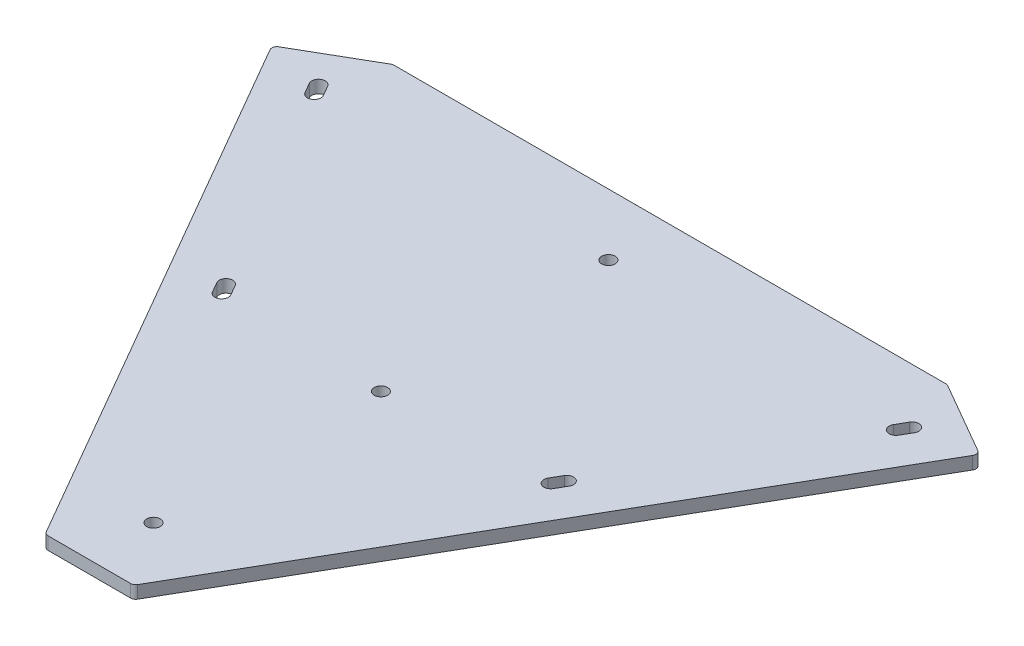
SolidWorks part; units mm, degrees
material "PC High Viscosity"
ref_plane "Front Plane" through (0, 0, 0) normal (0, 0, 1) x (1, 0, 0)
ref_plane "Top Plane" through (0, 0, 0) normal (0, 1, 0) x (1, 0, 0)
ref_plane "Right Plane" through (0, 0, 0) normal (1, 0, 0) x (0, 0, -1)
sketch "Sketch1" plane through (0, 0, 0) normal (0, 1, 0) x (1, 0, 0)
  line L0 (-95.25, 164.9778) -> (-56.7552, 187.2028) construction
  line L5 (-22.225, -99.5201) -> (22.225, -99.5201) construction
  line L6 (-22.225, -99.5201) -> (-22.225, 357.6799) construction
  line L7 (-22.225, 357.6799) -> (22.225, 357.6799) construction
  line L8 (22.225, -99.5201) -> (22.225, 357.6799) construction
  line L9 (-95.25, 164.9778) -> (-577.85, 1000.8656) construction
  line L10 (-56.7552, 187.2028) -> (-539.3552, 1023.0906) construction
  line L11 (-577.85, 1000.8656) -> (-539.3552, 1023.0906) construction
  line L16 (0, 0) -> (0, 1023.0906) construction
  line L17 (577.85, 1000.8656) -> (539.3552, 1023.0906) construction
  line L18 (56.7552, 187.2028) -> (539.3552, 1023.0906) construction
  line L19 (95.25, 164.9778) -> (577.85, 1000.8656) construction
  line L20 (95.25, 164.9778) -> (56.7552, 187.2028) construction
  line L21 (-155.1802, 357.6799) -> (-193.675, 335.4549) construction
  line L22 (-155.1802, 357.6799) -> (-177.4052, 396.1748) construction
  line L23 (-193.675, 335.4549) -> (-215.9, 373.9498) construction
  line L24 (-177.4052, 396.1748) -> (-215.9, 373.9498) construction
  line L25 (193.675, 335.4549) -> (215.9, 373.9498) construction
  line L26 (177.4052, 396.1748) -> (215.9, 373.9498) construction
  line L27 (155.1802, 357.6799) -> (177.4052, 396.1748) construction
  line L28 (155.1802, 357.6799) -> (193.675, 335.4549) construction
  line L29 (-177.8, 307.9586) -> (-22.225, 38.4948)
  line L30 (-22.225, 38.4948) -> (22.225, 38.4948)
  line L31 (-177.8, 307.9586) -> (-139.3052, 330.1836)
  line L32 (-139.3052, 330.1836) -> (139.3052, 330.1836)
  line L33 (177.8, 307.9586) -> (22.225, 38.4948)
  line L34 (177.8, 307.9586) -> (139.3052, 330.1836)
  point P18 (0, 357.6799)
  point P30 (0, 38.4948)
  point P32 (0, 330.1836)
  dimension "D1" = 60
  dimension "D2" = 965.2
  dimension "D3" = 190.5
  dimension "D4" = 44.45
  dimension "D5" = 196.85
  dimension "D6" = 34.5302
  dimension "D7" = 31.75
  dimension "D8" = 457.2
  dimension "D9" = 291.6888
  dimension "D10" = 311.15
extrude "Boss-Extrude1" add sketch "Sketch1" along normal blind 6.35
hole_wizard "1/4 Clearance Hole1" positions "Sketch2" profile "Sketch3" hole size "1/4" standard "ANSI Inch" end condition through all
sketch "Sketch2" plane through (0, 6.35, 0) normal (0, 1, 0) x (1, 0, 0)
  line L0 (0, 0) -> (0, 1023.0906) construction
  line L1 (0, 0) -> (0, 1023.0906) construction
  line L5 (-22.225, 38.4948) -> (22.225, 38.4948) construction
  point P22 (0, 70.6609)
  point P32 (0, 184.9609)
  point P33 (0, 299.2609)
  dimension "D4" = 32.1661
  dimension "D5" = 114.3
  dimension "D3" = 3
sketch "Sketch3" plane through (0, 6.35, -299.2609) normal (1, 0, 0) x (0, 0, 1)
  line L0 (0, 0) -> (0, 6.35)
  line L1 (0, 6.35) -> (3.3782, 6.35)
  line L2 (3.3782, 6.35) -> (3.3782, 0)
  line L5 (3.3782, 0) -> (0, 0)
  line L11 (0, -6.35) -> (0, 107.95) construction
  dimension "Thru Hole Dia." = 6.7564
  dimension "Thru Hole Depth" = 6.35
sketch "Sketch6" plane through (0, 6.35, 0) normal (0, 1, 0) x (1, 0, 0)
  line L0 (-149.1165, 302.7273) -> (-146.1447, 297.58) construction
  line L1 (-146.1909, 304.4164) -> (-143.2191, 299.2691)
  line L2 (-152.0421, 301.0382) -> (-149.0703, 295.8909)
  line L3 (-158.5526, 319.0711) -> (3.4382, 38.4948) construction
  line L4 (-139.3052, 330.1836) -> (-177.8, 307.9586) construction
  line L5 (-22.225, 38.4948) -> (22.225, 38.4948) construction
  line L6 (0, 330.1836) -> (0, 38.4948) construction
  line L7 (139.3052, 330.1836) -> (-139.3052, 330.1836) construction
  line L8 (-177.8, 307.9586) -> (-22.225, 38.4948) construction
  line L9 (-82.6447, 187.5948) -> (-85.6165, 192.7421) construction
  line L10 (-85.5703, 185.9057) -> (-88.5421, 191.053)
  line L11 (-79.7191, 189.2839) -> (-82.6909, 194.4312)
  line L12 (-95.25, 164.9778) -> (-56.7552, 187.2028) construction
  line L13 (149.1165, 302.7273) -> (146.1447, 297.58) construction
  line L14 (146.1909, 304.4164) -> (143.2191, 299.2691)
  line L15 (152.0421, 301.0382) -> (149.0703, 295.8909)
  line L16 (82.6447, 187.5948) -> (85.6165, 192.7421) construction
  line L17 (85.5703, 185.9057) -> (88.5421, 191.053)
  line L18 (79.7191, 189.2839) -> (82.6909, 194.4312)
  arc A0 (-146.1909, 304.4164) -> (-152.0421, 301.0382) centre (-149.1165, 302.7273) ccw
  arc A1 (-149.0703, 295.8909) -> (-143.2191, 299.2691) centre (-146.1447, 297.58) ccw
  arc A2 (-85.5703, 185.9057) -> (-79.7191, 189.2839) centre (-82.6447, 187.5948) ccw
  arc A3 (-82.6909, 194.4312) -> (-88.5421, 191.053) centre (-85.6165, 192.7421) ccw
  arc A4 (146.1909, 304.4164) -> (152.0421, 301.0382) centre (149.1165, 302.7273) cw
  arc A5 (149.0703, 295.8909) -> (143.2191, 299.2691) centre (146.1447, 297.58) cw
  arc A6 (85.5703, 185.9057) -> (79.7191, 189.2839) centre (82.6447, 187.5948) cw
  arc A7 (82.6909, 194.4312) -> (88.5421, 191.053) centre (85.6165, 192.7421) cw
  point P2 (-147.6306, 300.1537)
  point P19 (-84.1306, 190.1684)
  point P30 (147.6306, 300.1537)
  point P37 (84.1306, 190.1684)
  dimension "D1" = 3.3782
  dimension "D3" = 12.7
  dimension "D2" = 21.844
  dimension "D4" = 16.256
extrude "Cut-Extrude1" cut sketch "Sketch6" against normal through all
fillet "Fillet1" radius 2.54 6 edges at (22.225, 3.175, -38.4948) (-22.225, 3.175, -38.4948) (-139.3052, 3.175, -330.1836) (139.3052, 3.175, -330.1836) (177.8, 3.175, -307.9586) (-177.8, 3.175, -307.9586)
